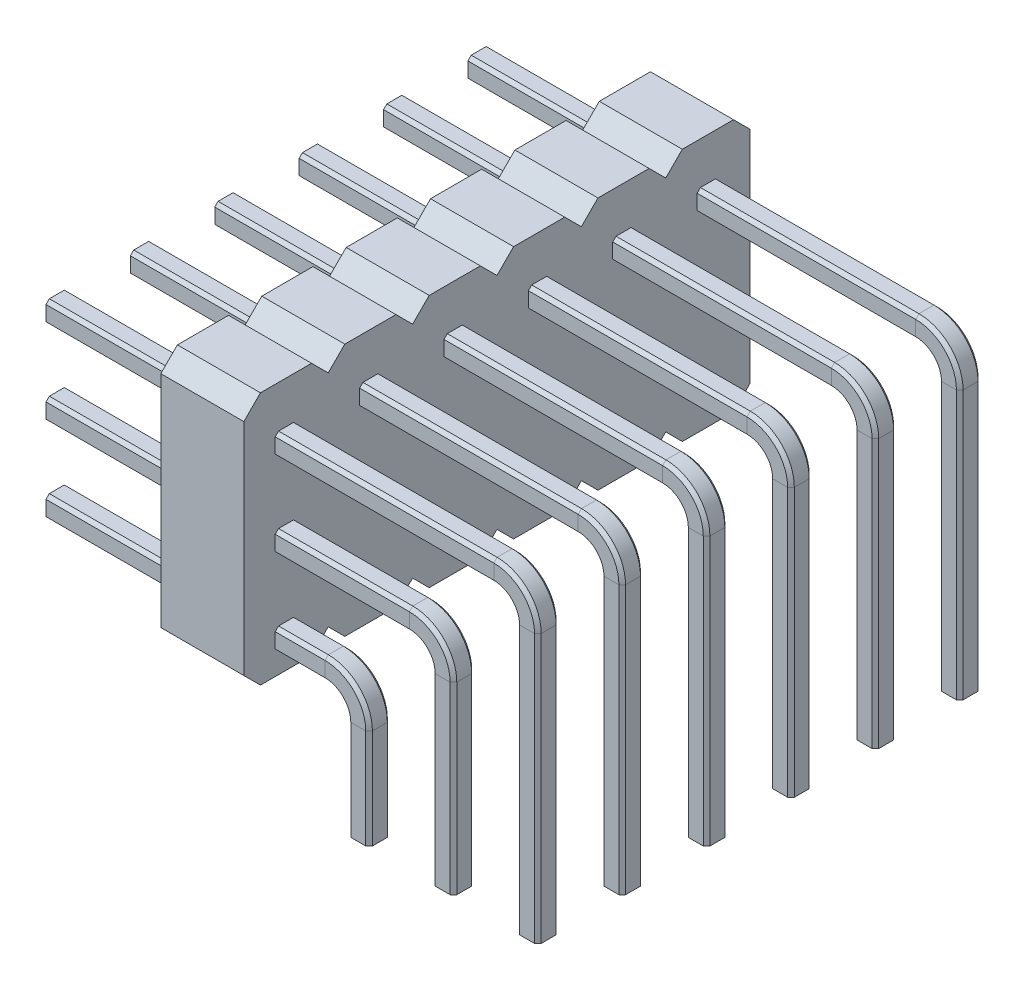
SolidWorks part; units mm, degrees
ref_plane "Front Plane" through (0, 0, 0) normal (0, 0, 1) x (1, 0, 0)
ref_plane "Top Plane" through (0, 0, 0) normal (0, 1, 0) x (1, 0, 0)
ref_plane "Right Plane" through (0, 0, 0) normal (1, 0, 0) x (0, 0, -1)
sketch "Sketch1" plane through (0, 0, 0) normal (0, 1, 0) x (1, 0, 0)
  line L0 (-0.325, 0.225) -> (-0.225, 0.325)
  line L1 (-0.225, 0.325) -> (0.225, 0.325)
  line L2 (-0.325, 0.225) -> (-0.325, -0.225)
  line L3 (-0.225, -0.325) -> (0.225, -0.325)
  line L4 (0.325, 0.225) -> (0.325, -0.225)
  line L5 (-0.325, 0.325) -> (0.325, -0.325) construction
  line L6 (-0.325, -0.325) -> (0.325, 0.325) construction
  line L7 (0.225, 0.325) -> (0.325, 0.225)
  line L8 (-0.325, -0.225) -> (-0.225, -0.325)
  line L9 (0.225, -0.325) -> (0.325, -0.225)
  line L10 (2.315, 0.325) -> (2.765, 0.325)
  line L11 (2.215, 0.225) -> (2.315, 0.325)
  line L12 (2.215, 0.225) -> (2.215, -0.225)
  line L13 (2.215, -0.225) -> (2.315, -0.325)
  line L14 (2.315, -0.325) -> (2.765, -0.325)
  line L15 (2.765, -0.325) -> (2.865, -0.225)
  line L16 (2.865, 0.225) -> (2.865, -0.225)
  line L17 (4.855, 0.325) -> (5.305, 0.325)
  line L18 (4.755, 0.225) -> (4.855, 0.325)
  line L19 (4.755, 0.225) -> (4.755, -0.225)
  line L20 (4.755, -0.225) -> (4.855, -0.325)
  line L21 (4.855, -0.325) -> (5.305, -0.325)
  line L22 (5.305, -0.325) -> (5.405, -0.225)
  line L23 (5.405, 0.225) -> (5.405, -0.225)
  line L24 (2.765, 0.325) -> (2.865, 0.225)
  line L25 (5.305, 0.325) -> (5.405, 0.225)
  point P0 (0, 0)
  dimension "D1" = 0.65
  dimension "D2" = 3
  dimension "D3" = 3
sketch "Sketch2" plane through (0, 0, 0) normal (0, 0, 1) x (1, 0, 0)
  line L0 (5.08, 0) -> (5.08, 8.08)
  line L1 (4.855, 0) -> (5.305, 0) construction
  line L2 (4.08, 9.08) -> (-9.4, 9.08)
  line L3 (2.54, 0) -> (2.54, 5.54)
  line L4 (2.315, 0) -> (2.765, 0) construction
  line L5 (1.54, 6.54) -> (-9.4, 6.54)
  line L6 (0, 0) -> (0, 3)
  line L7 (-1, 4) -> (-9.4, 4)
  arc A0 (0, 3) -> (-1, 4) centre (-1, 3) ccw
  arc A1 (2.54, 5.54) -> (1.54, 6.54) centre (1.54, 5.54) ccw
  arc A2 (5.08, 8.08) -> (4.08, 9.08) centre (4.08, 8.08) ccw
  point P13 (0, 0)
  point P15 (-9.4, 6.54)
  point P18 (0, 4)
  point P21 (2.54, 6.54)
  point P24 (5.08, 9.08)
  dimension "D5" = 1
  dimension "D1" = 9.08
  dimension "D2" = 14.48
  dimension "D3" = 6.54
  dimension "D4" = 4
sweep "Sweep1" add profiles "Sketch1" path "Sketch2"
sweep "Sweep2" add profiles "Sketch1<3>" path "Sketch2<3>"
sketch "Sketch1<3>" plane through (0, 0, 0) normal (0, 1, 0) x (1, 0, 0) same geometry as "Sketch1"
sketch "Sketch2<3>" plane through (0, 0, 0) normal (0, 0, 1) x (1, 0, 0) same geometry as "Sketch2"
sweep "Sweep3" add profiles "Sketch1<4>" path "Sketch2<4>"
sketch "Sketch1<4>" plane through (0, 0, 0) normal (0, 1, 0) x (1, 0, 0) same geometry as "Sketch1"
sketch "Sketch2<4>" plane through (0, 0, 0) normal (0, 0, 1) x (1, 0, 0) same geometry as "Sketch2"
ref_plane "Plane1" through (-2.5, 0, 0) normal (1, 0, 0) x (0, 0, -1)
sketch "Sketch3" plane through (-2.5, 0, 0) normal (1, 0, 0) x (0, 0, -1)
  line L0 (0, 11.0325) -> (0, 2.5254) construction
  line L1 (0, 0) -> (0, 3) construction
  line L2 (0.225, 9.405) -> (-0.225, 9.405) construction
  line L3 (-0.77, 10.675) -> (0.77, 10.675)
  line L4 (-1.27, 10.175) -> (-1.27, 3.555)
  line L5 (-0.77, 3.055) -> (0.77, 3.055)
  line L6 (1.27, 10.175) -> (1.27, 3.555)
  line L7 (-1.27, 10.675) -> (1.27, 3.055) construction
  line L8 (-1.27, 3.055) -> (1.27, 10.675) construction
  line L9 (0, 0) -> (0, 8.08) construction
  line L10 (-1.27, 10.175) -> (-0.77, 10.675)
  line L11 (0.77, 10.675) -> (1.27, 10.175)
  line L12 (-1.27, 3.555) -> (-0.77, 3.055)
  line L13 (0.77, 3.055) -> (1.27, 3.555)
  point P4 (0, 6.865)
  point P11 (0, 0)
  dimension "D1" = 7.62
  dimension "D2" = 1.27
  dimension "D3" = 2.54
extrude "Boss-Extrude1" add sketch "Sketch3" against normal blind 2.5
pattern_linear "LPattern1" count 6 spacing 2.54 along (0, 0, 1) of bodies 104
combine bodies "Combine1" operation type add bodies to combine 104 105 106 107 108 109
